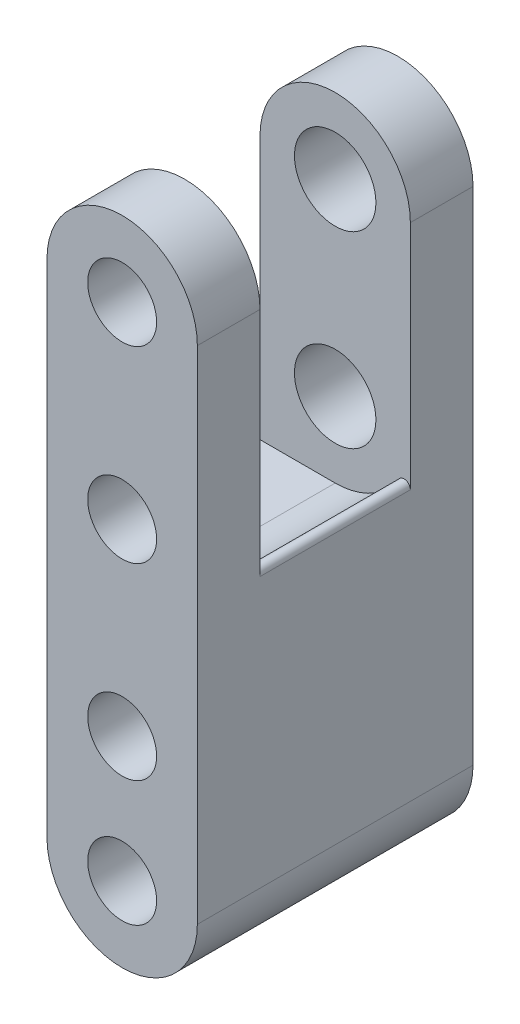
SolidWorks part; units mm, degrees
material "ABS"
ref_plane "Front Plane" through (0, 0, 0) normal (0, 0, 1) x (1, 0, 0)
ref_plane "Top Plane" through (0, 0, 0) normal (0, 1, 0) x (1, 0, 0)
ref_plane "Right Plane" through (0, 0, 0) normal (1, 0, 0) x (0, 0, -1)
ref_axis "X" through (-88.99, 0, 0) along (1, 0, 0)
ref_axis "Y" through (0, 55, 0) along (0, -1, 0)
ref_axis "Z" through (0, 0, -88.99) along (0, 0, 1)
sketch "Sketch1" plane through (0, 0, 0) normal (0, 0, 1) x (1, 0, 0)
  line L0 (0, 0) -> (0, -40) construction
  line L4 (6, 0) -> (6, -40)
  line L5 (-6, 0) -> (-6, -40)
  line L6 (0, -21) -> (-6, -21)
  circle A0 centre (0, 0) radius 3.25
  circle A1 centre (0, -15) radius 3.25
  arc A3 (6, 0) -> (-6, 0) centre (0, 0) ccw
  arc A4 (-6, -40) -> (6, -40) centre (0, -40) ccw
  arc A5 (0, -21) -> (6, -15) centre (0, -15) ccw
  circle A6 centre (0, -40) radius 3.25 construction
  circle A7 centre (0, -30) radius 3.25 construction
  point P5 (0, -20)
  point P18 (0, -18)
  point P19 (0, -30)
  point P20 (2.8148, -16.0377)
  dimension "D1" = 6.5
  dimension "D2" = 15
  dimension "D4" = 6
  dimension "D5" = 10
  dimension "D3" = 40
extrude "Boss-Extrude1" add sketch "Sketch1" along normal mid plane 22 contours A5 L6 L5 A4 L4 | L6 A5 L4 A3 L5 | A1 | A0 region at (-0.1535, -7.9007, 0) region at (0.1232, -32.5442, 0) region at (0, 0, 0) region at (0, -15, 0)
sketch "Sketch4" plane through (0, 0, 11) normal (0, 0, 1) x (1, 0, 0)
  point P0 (0, 0)
  point P3 (0, -15)
  point P6 (0, -30)
  point P9 (0, -40)
hole_wizard "M5 Clearance Hole1" positions "Sketch4" profile "Sketch3" hole size "M5" standard "ANSI Metric" end condition through all
sketch "Sketch3" plane through (0, 0, 11) normal (1, 0, 0) x (0, -1, 0)
  line L0 (0, 0) -> (0, 22)
  line L1 (0, 22) -> (2.75, 22)
  line L2 (2.75, 22) -> (2.75, 0)
  line L5 (2.75, 0) -> (0, 0)
  line L11 (0, -6.35) -> (0, 107.95) construction
  dimension "Thru Hole Dia." = 5.5
  dimension "Thru Hole Depth" = 22
extrude "Cut-Extrude1" cut sketch "Sketch1<3>" against normal mid plane 12 contours L6 A5 L4 A3 L5 | A0 | A1 region at (-0.1535, -7.9007, 0)
sketch "Sketch1<3>" plane through (0, 0, 0) normal (0, 0, 1) x (1, 0, 0) same geometry as "Sketch1"
extrude "Cut-Extrude2" cut sketch "Sketch1<4>" against normal through all contours A0 | A1
sketch "Sketch1<4>" plane through (0, 0, 0) normal (0, 0, 1) x (1, 0, 0) same geometry as "Sketch1"
fillet "Fillet1" radius 0.5 1 edges at (6, -15, 0)
